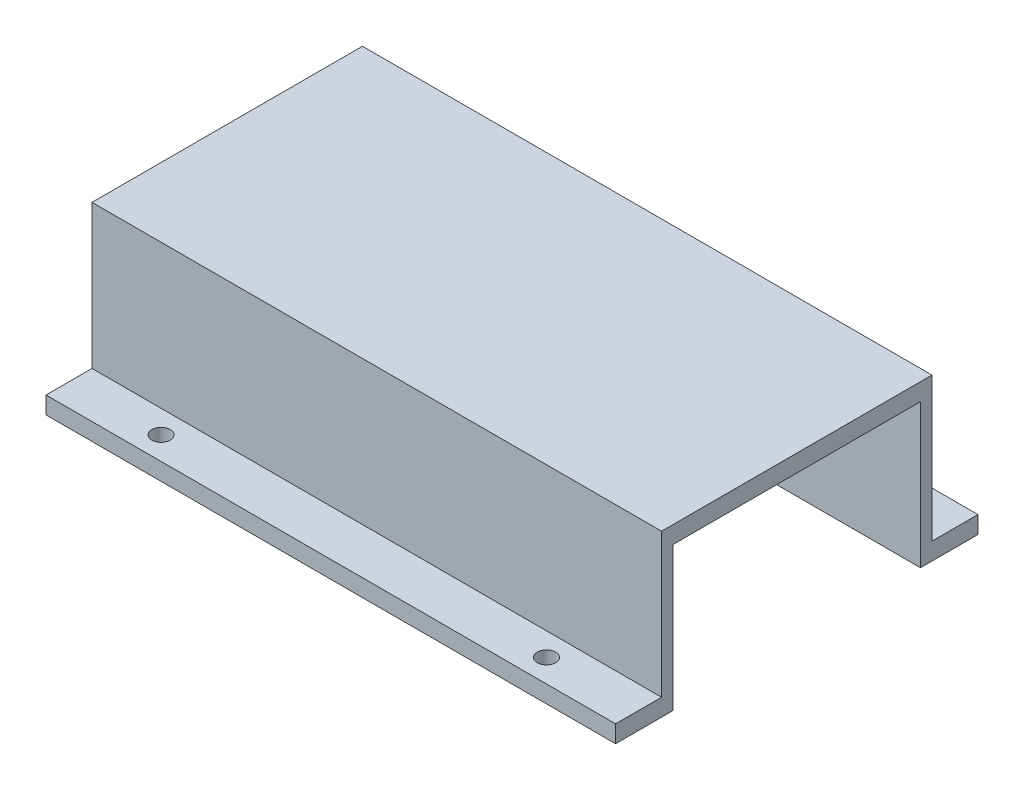
SolidWorks part; units mm, degrees
ref_plane "Płaszczyzna przednia" through (0, 0, 0) normal (0, 0, 1) x (1, 0, 0)
ref_plane "Płaszczyzna górna" through (0, 0, 0) normal (0, 1, 0) x (1, 0, 0)
ref_plane "Płaszczyzna prawa" through (0, 0, 0) normal (1, 0, 0) x (0, 0, -1)
sketch "Sketch1" plane through (0, 0, 0) normal (0, 1, 0) x (1, 0, 0)
  line L0 (49.5, 23.5) -> (-49.5, 23.5)
  line L1 (49.5, 21.5) -> (-49.5, 21.5)
  line L2 (49.5, 21.5) -> (49.5, -21.5)
  line L3 (49.5, -21.5) -> (-49.5, -21.5)
  line L4 (-49.5, 21.5) -> (-49.5, -21.5)
  line L5 (49.5, 21.5) -> (-49.5, -21.5) construction
  line L6 (49.5, -21.5) -> (-49.5, 21.5) construction
  line L7 (49.5, -23.5) -> (-49.5, -23.5)
  line L8 (-49.5, 23.5) -> (-49.5, 21.5)
  line L9 (-49.5, -21.5) -> (-49.5, -23.5)
  line L10 (0, 26.492) -> (0, -26.492) construction
  line L11 (49.5, -21.5) -> (49.5, -23.5)
  line L12 (49.5, 23.5) -> (49.5, 21.5)
  point P0 (0, 0)
  dimension "D1" = 99
  dimension "43" = 43
  dimension "D3" = 2
  dimension "D2" = 2
extrude "Boss-Extrude1" add sketch "Sketch1" along normal blind 3 contours L1 L4 L3 L2 | L11 L3 L9 L7 | L12 L0 L8 L1 region at (0, 0, -22.5) region at (0, 0, 0) region at (0, 0, 22.5)
extrude "Boss-Extrude2" add sketch "Sketch1<5>" against normal blind 25 contours L11 L3 L9 L7 | L12 L0 L8 L1 region at (0, 0, -22.5) region at (0, 0, 22.5)
sketch "Sketch1<5>" plane through (0, 0, 0) normal (0, 1, 0) x (1, 0, 0) same geometry as "Sketch1"
sketch "Sketch3" plane through (0, -25, 0) normal (0, -1, 0) x (1, 0, 0)
  line L0 (-71.4003, 0) -> (59.2521, 0) construction
  line L2 (-49.5, 31.5) -> (49.5, 31.5)
  line L3 (-49.5, 31.5) -> (-49.5, 23.5)
  line L4 (-49.5, 23.5) -> (49.5, 23.5)
  line L5 (49.5, 31.5) -> (49.5, 23.5)
  line L6 (0, 49.8837) -> (0, -42.3933) construction
  line L7 (-49.5, -23.5) -> (49.5, -23.5)
  line L8 (49.5, -31.5) -> (49.5, -23.5)
  line L9 (-49.5, -31.5) -> (49.5, -31.5)
  line L10 (-49.5, -31.5) -> (-49.5, -23.5)
  circle A0 centre (-33.5, 27.5) radius 1.6
  circle A1 centre (33.5, 27.5) radius 1.6
  circle A2 centre (33.5, -27.5) radius 1.6
  circle A3 centre (-33.5, -27.5) radius 1.6
  dimension "D2" = 3.2
  dimension "D1" = 8
  dimension "D3" = 16
  dimension "D4" = 4
extrude "Boss-Extrude3" add sketch "Sketch3" against normal blind 3
